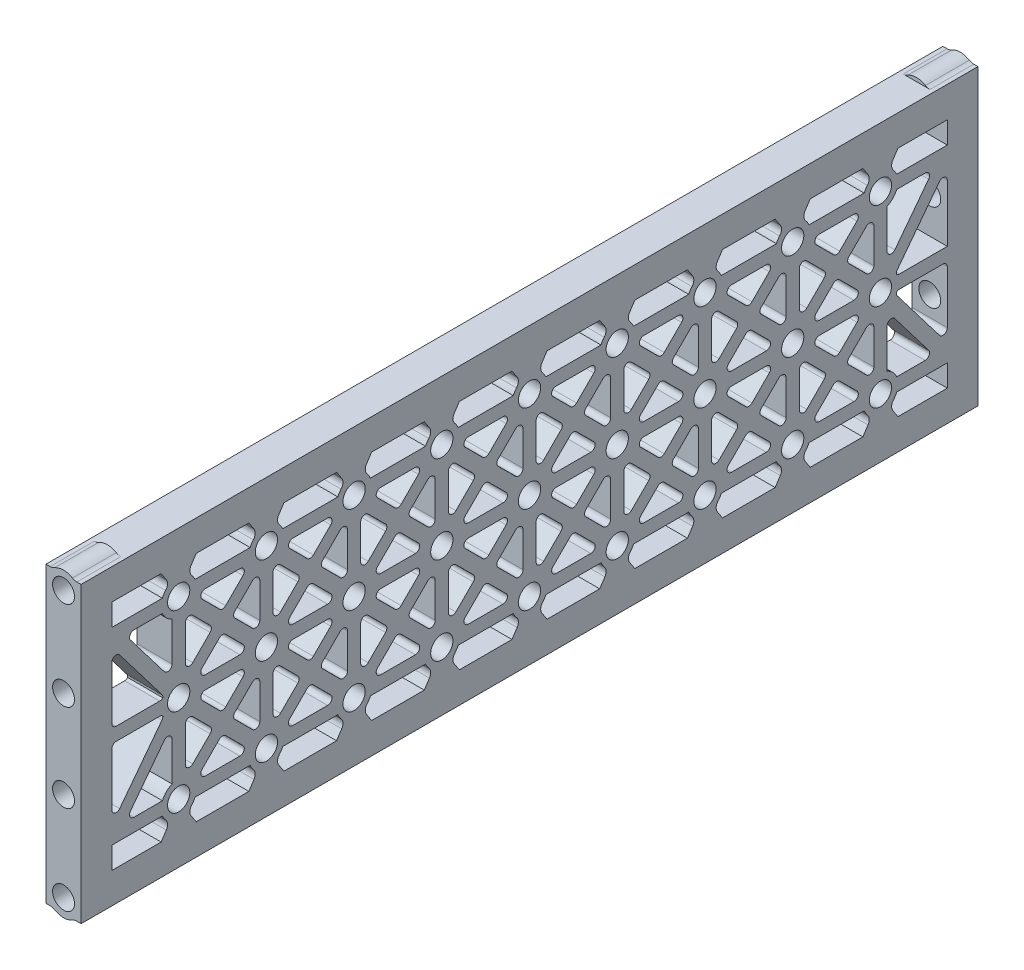
SolidWorks part; units mm, degrees
ref_plane "Front Plane" through (0, 0, 0) normal (0, 0, 1) x (1, 0, 0)
ref_plane "Top Plane" through (0, 0, 0) normal (0, 1, 0) x (1, 0, 0)
ref_plane "Right Plane" through (0, 0, 0) normal (1, 0, 0) x (0, 0, -1)
sketch "Sketch1" plane through (-219.25, 0, 0) normal (-1, 0, 0) x (0, 0, 1)
  line L1 (102.25, 62) -> (-102.25, 62)
  line L2 (102.25, 62) -> (102.25, -5)
  line L3 (102.25, -5) -> (-102.25, -5)
  line L4 (-102.25, 62) -> (-102.25, -5)
  line L5 (102.25, 1.35) -> (102.25, -6.9319) construction
  line L6 (110.25, 62) -> (102.25, 62) construction
  line L7 (-102.25, -5) -> (-102.25, 0) construction
  line L8 (-102.25, -5) -> (-110.25, -5) construction
extrude "Boss-Extrude1" add sketch "Sketch1" against normal blind 8
hole_wizard "Ø5.0mm Dowel Hole1" positions "Sketch4" profile "Sketch3" hole size "Ø5.0" standard "ANSI Metric"
sketch "Sketch4" plane through (0, 0, 102.25) normal (0, 0, 1) x (1, 0, 0)
  point P0 (-215.25, 58.825)
  point P3 (-215.25, 38.5)
  point P6 (-215.25, 18.5)
  point P9 (-215.25, -1.825)
sketch "Sketch3" plane through (-215.25, 58.825, 102.25) normal (1, 0, 0) x (0, -1, 0)
  line L0 (0, 0) -> (0, 11.5022)
  line L1 (0, 11.5022) -> (2.5, 10)
  line L2 (2.5, 10) -> (2.5, 0)
  line L5 (2.5, 0) -> (0, 0)
  line L10 (0, 11.5022) -> (-2.5, 10) construction
  line L11 (0, -6.35) -> (0, 107.95) construction
  dimension "Hole Dia." = 5
  dimension "Hole Depth" = 10
  dimension "Drill Angle" = 118
sketch "Sketch5" plane through (0, 0, 102.25) normal (0, 0, 1) x (1, 0, 0)
  circle A0 centre (-215.25, 58.825) radius 4
  circle A1 centre (-215.25, -1.825) radius 4
  line M6 (-219.25, -5) -> (-211.25, -5)
  line M8 (-211.25, 62) -> (-219.25, 62)
extrude "Boss-Extrude2" add sketch "Sketch5" against normal blind 10 contours A1 M6 | A0 M8 region at (-215.25, 62.3331, 102.25) region at (-215.25, -5.3331, 102.25)
fillet "Fillet1" radius 2 4 edges at (-212.817, -5, 97.25) (-217.683, -5, 97.25) (-212.817, 62, 97.25) (-217.683, 62, 97.25)
mirror "Mirror1" about plane through (0, 0, 0) normal (0, 0, 1) of "Fillet1", "Boss-Extrude2", "Ø5.0mm Dowel Hole1"
sketch "Sketch6" plane through (-219.25, 0, 0) normal (-1, 0, 0) x (0, 0, 1)
  line L0 (0, 8.5) -> (0, 28.5) construction
  line L1 (0, 48.5) -> (0, 55) construction
  line L2 (0, 8.5) -> (20, 8.5) construction
  line L3 (0, -4.4) -> (0, 4.4) construction
  line L10 (0, 8.5) -> (0, 2) construction
  line L14 (95.25, 2) -> (95.25, 55)
  line L15 (-95.25, 2) -> (95.25, 2)
  line L16 (-95.25, 55) -> (-95.25, 2)
  line L17 (95.25, 55) -> (-95.25, 55)
  line L18 (95.25, 2) -> (95.25, 55)
  line L19 (-95.25, 2) -> (95.25, 2)
  line L20 (-95.25, 55) -> (-95.25, 2)
  line L21 (95.25, 55) -> (-95.25, 55)
  circle A0 centre (0, 8.5) radius 2.54
  circle A1 centre (0, 28.5) radius 2.54
  circle A2 centre (0, 48.5) radius 2.54
  circle A3 centre (0, 48.5) radius 4
  circle A4 centre (0, 28.5) radius 4
  circle A5 centre (0, 8.5) radius 4
  circle A6 centre (20, 8.5) radius 4
  circle A7 centre (20, 8.5) radius 2.54
  circle A8 centre (20, 28.5) radius 4
  circle A9 centre (20, 28.5) radius 2.54
  circle A10 centre (20, 48.5) radius 2.54
  circle A11 centre (20, 48.5) radius 4
  circle A12 centre (40, 8.5) radius 4
  circle A13 centre (40, 8.5) radius 2.54
  circle A14 centre (40, 28.5) radius 4
  circle A15 centre (40, 28.5) radius 2.54
  circle A16 centre (40, 48.5) radius 2.54
  circle A17 centre (40, 48.5) radius 4
  circle A18 centre (60, 8.5) radius 4
  circle A19 centre (60, 8.5) radius 2.54
  circle A20 centre (60, 28.5) radius 4
  circle A21 centre (60, 28.5) radius 2.54
  circle A22 centre (60, 48.5) radius 2.54
  circle A23 centre (60, 48.5) radius 4
  circle A24 centre (80, 8.5) radius 4
  circle A25 centre (80, 8.5) radius 2.54
  circle A26 centre (80, 28.5) radius 4
  circle A27 centre (80, 28.5) radius 2.54
  circle A28 centre (80, 48.5) radius 2.54
  circle A29 centre (80, 48.5) radius 4
  circle A30 centre (-20, 8.5) radius 4
  circle A31 centre (-20, 8.5) radius 2.54
  circle A32 centre (-40, 8.5) radius 4
  circle A33 centre (-40, 8.5) radius 2.54
  circle A34 centre (-60, 8.5) radius 4
  circle A35 centre (-60, 8.5) radius 2.54
  circle A36 centre (-80, 8.5) radius 4
  circle A37 centre (-80, 8.5) radius 2.54
  circle A38 centre (-80, 48.5) radius 2.54
  circle A39 centre (-80, 48.5) radius 4
  circle A40 centre (-80, 28.5) radius 4
  circle A41 centre (-80, 28.5) radius 2.54
  circle A42 centre (-60, 28.5) radius 2.54
  circle A43 centre (-60, 28.5) radius 4
  circle A44 centre (-40, 28.5) radius 4
  circle A45 centre (-40, 28.5) radius 2.54
  circle A46 centre (-20, 28.5) radius 4
  circle A47 centre (-20, 28.5) radius 2.54
  circle A48 centre (-20, 48.5) radius 2.54
  circle A49 centre (-20, 48.5) radius 4
  circle A50 centre (-40, 48.5) radius 2.54
  circle A51 centre (-40, 48.5) radius 4
  circle A52 centre (-60, 48.5) radius 4
  circle A53 centre (-60, 48.5) radius 2.54
  dimension "D2" = 5.08
  dimension "D5" = 8
  dimension "D4" = 20
  dimension "D7" = 20
  dimension "D1" = 7
  dimension "D3" = 3
  dimension "D6" = 5
extrude "Cut-Extrude1" cut sketch "Sketch6" against normal through all contours L18 L21 L20 L19 A51 A49 A46 A43 A40 A34 A30 A29 A26 A24 A23 A20 A18 A17 A14 A12 A11 A8 A6 A5 A4 A3 A32 | A38 | A53 | A50 | A48 | A47 | A45 | A42 | A41 | A0 | A1 | A2 | A9 | A7 | A31 | A33 | A35 | A37 | A16 | A22 | A28 | A10 | A15 | A21 | A27 | A25 | A19 | A13 region at (-219.25, 3.9774, 0) region at (-219.25, 8.5, 0) region at (-219.25, 28.5, 0) region at (-219.25, 48.5, 0) region at (-219.25, 8.5, 20) region at (-219.25, 28.5, 20) region at (-219.25, 48.5, 20) region at (-219.25, 8.5, 40) region at (-219.25, 28.5, 40) region at (-219.25, 48.5, 40) region at (-219.25, 8.5, 60) region at (-219.25, 28.5, 60) region at (-219.25, 48.5, 60) region at (-219.25, 8.5, 80) region at (-219.25, 28.5, 80) region at (-219.25, 48.5, 80) region at (-219.25, 8.5, -20) region at (-219.25, 8.5, -40) region at (-219.25, 8.5, -60) region at (-219.25, 8.5, -80) region at (-219.25, 48.5, -80) region at (-219.25, 28.5, -80) region at (-219.25, 28.5, -60) region at (-219.25, 28.5, -40) region at (-219.25, 28.5, -20) region at (-219.25, 48.5, -20) region at (-219.25, 48.5, -40) region at (-219.25, 48.5, -60)
sketch "Sketch7" plane through (-219.25, 0, 0) normal (-1, 0, 0) x (0, 0, 1)
  line L0 (80, 45.96) -> (80, 31.04) construction
  line L1 (60, 45.96) -> (60, 31.04) construction
  line L2 (62.54, 48.5) -> (77.46, 48.5) construction
  line L3 (62.54, 28.5) -> (77.46, 28.5) construction
  line L4 (70, 38.5) -> (78.2039, 46.7039) construction
  line L5 (61.7961, 46.7039) -> (70, 38.5) construction
  line L6 (61.7961, 30.2961) -> (70, 38.5) construction
  line L7 (70, 38.5) -> (78.2039, 30.2961) construction
  line L8 (65.3284, 45.2929) -> (69.2929, 41.3284)
  line L9 (70.7071, 41.3284) -> (74.6716, 45.2929)
  line L10 (66.0355, 47) -> (73.9645, 47)
  line L11 (62.8567, 47.7646) -> (70, 40.6213) construction
  line L12 (62.54, 47) -> (77.46, 47) construction
  line L13 (70, 40.6213) -> (77.1433, 47.7646) construction
  line L14 (76.7929, 43.1716) -> (72.8284, 39.2071)
  line L15 (72.8284, 37.7929) -> (76.7929, 33.8284)
  line L16 (78.5, 42.4645) -> (78.5, 34.5355)
  line L17 (74.6716, 31.7071) -> (70.7071, 35.6716)
  line L18 (69.2929, 35.6716) -> (65.3284, 31.7071)
  line L19 (73.9645, 30) -> (66.0355, 30)
  line L20 (63.2071, 33.8284) -> (67.1716, 37.7929)
  line L21 (67.1716, 39.2071) -> (63.2071, 43.1716)
  line L22 (61.5, 34.5355) -> (61.5, 42.4645)
  line L23 (63.7081, 50) -> (76.2919, 50)
  line L24 (81.5, 44.7919) -> (81.5, 32.2081)
  line L25 (58.5, 44.7919) -> (58.5, 32.2081)
  line L26 (62.54, 27) -> (76.2919, 27)
  line L27 (62.54, 50) -> (77.46, 50) construction
  line L28 (58.5, 45.96) -> (58.5, 31.04) construction
  line L29 (81.5, 45.96) -> (81.5, 31.04) construction
  line L30 (62.54, 27) -> (77.46, 27) construction
  circle A0 centre (80, 48.5) radius 2.54 construction
  circle A1 centre (80, 28.5) radius 2.54 construction
  circle A2 centre (60, 48.5) radius 2.54 construction
  circle A3 centre (60, 28.5) radius 2.54 construction
  arc A4 (80, 31.04) -> (77.46, 28.5) centre (80, 28.5) ccw construction
  arc A5 (77.46, 48.5) -> (80, 45.96) centre (80, 48.5) ccw construction
  arc A6 (60, 45.96) -> (62.54, 48.5) centre (60, 48.5) ccw construction
  arc A7 (62.54, 28.5) -> (60, 31.04) centre (60, 28.5) ccw construction
  arc A8 (73.9645, 47) -> (74.6716, 45.2929) centre (73.9645, 46) cw
  arc A9 (70.7071, 41.3284) -> (69.2929, 41.3284) centre (70, 42.0355) cw
  arc A10 (65.3284, 45.2929) -> (66.0355, 47) centre (66.0355, 46) cw
  arc A11 (76.7929, 43.1716) -> (78.5, 42.4645) centre (77.5, 42.4645) cw
  arc A12 (72.8284, 37.7929) -> (72.8284, 39.2071) centre (73.5355, 38.5) cw
  arc A13 (78.5, 34.5355) -> (76.7929, 33.8284) centre (77.5, 34.5355) cw
  arc A14 (74.6716, 31.7071) -> (73.9645, 30) centre (73.9645, 31) cw
  arc A15 (69.2929, 35.6716) -> (70.7071, 35.6716) centre (70, 34.9645) cw
  arc A16 (66.0355, 30) -> (65.3284, 31.7071) centre (66.0355, 31) cw
  arc A17 (63.2071, 33.8284) -> (61.5, 34.5355) centre (62.5, 34.5355) cw
  arc A18 (67.1716, 39.2071) -> (67.1716, 37.7929) centre (66.4645, 38.5) cw
  arc A19 (61.5, 42.4645) -> (63.2071, 43.1716) centre (62.5, 42.4645) cw
  circle A20 centre (60, 28.5) radius 4 construction
  circle A21 centre (80, 28.5) radius 4 construction
  circle A22 centre (80, 48.5) radius 4 construction
  circle A23 centre (60, 48.5) radius 4 construction
  circle A24 centre (60, 28.5) radius 4
  circle A25 centre (80, 28.5) radius 4
  circle A26 centre (80, 48.5) radius 4
  circle A27 centre (60, 48.5) radius 4
  point P40 (70, 38.5)
  point P69 (70, 38.5)
  circle M37 centre (80, 48.5) radius 4
  dimension "D3" = 1
  dimension "D1" = 1.5
  dimension "D2" = 1.5
  dimension "D5" = 1.5
  dimension "D6" = 1.5
  dimension "D4" = 4
extrude "Boss-Extrude3" add sketch "Sketch7" against normal up to surface (8 mm away) contours A27 L25 A24 L26 A25 L24 L23 L8 A10 L10 A8 L9 A9 L16 A13 L15 A12 L14 A11 L19 A16 L18 A15 L17 A14 L22 A19 L21 A18 L20 A17 M37 region at (-219.25, 38.5, 70) up to face at (-211.25, 48.5, 64)
pattern_linear "LPattern1" count 8 spacing 20 along (0, 0, -1) count 2 spacing 20 along (0, -1, 0) of "Boss-Extrude3"
sketch "Sketch8" plane through (-219.25, 0, 0) normal (-1, 0, 0) x (0, 0, 1)
  line L0 (80, 48.5) -> (95.25, 48.5) construction
  line L1 (95.25, 2) -> (95.25, 55) construction
  line L2 (80, 28.5) -> (95.25, 28.5) construction
  line L3 (80, 8.5) -> (95.25, 8.5) construction
  line L4 (83.7081, 47) -> (92.2199, 47)
  line L6 (80, 28.5) -> (95.25, 48.5) construction
  line L7 (80, 28.5) -> (95.25, 8.5) construction
  line L8 (81.0556, 32.3582) -> (92.2199, 47)
  line L9 (80, 10) -> (92.2199, 10) construction
  line L10 (81.0556, 24.6418) -> (92.2199, 10)
  line L11 (83.7081, 10) -> (92.2199, 10)
  line L12 (83.7081, 50) -> (95.25, 50)
  line L13 (83.7081, 27) -> (95.25, 27)
  line L14 (81.1928, 29.4095) -> (98.2801, 7) construction
  line L15 (83.4412, 26.4608) -> (95.25, 10.9738)
  line L16 (83.7081, 7) -> (95.25, 7)
  line L17 (95.25, 50) -> (95.25, 7)
  line L18 (80, 50) -> (98.2801, 50) construction
  line L19 (80, 47) -> (92.2199, 47) construction
  line L20 (78.8072, 29.4095) -> (92.2199, 47) construction
  line L21 (83.7081, 30) -> (95.25, 30)
  line L23 (83.4412, 30.5392) -> (95.25, 46.0262)
  line L24 (81.1928, 27.5905) -> (98.2801, 50) construction
  line L25 (78.8072, 27.5905) -> (92.2199, 10) construction
  line L26 (80, 7) -> (98.2801, 7) construction
  circle A5 centre (80, 28.5) radius 4
  circle A6 centre (80, 48.5) radius 4
  circle A7 centre (80, 8.5) radius 4
  line M14 (95.25, 55) -> (95.25, 2)
  dimension "D1" = 1.5
  dimension "D2" = 1.5
extrude "Boss-Extrude4" add sketch "Sketch8" against normal up to surface (8 mm away) contours A6 L4 L8 A5 L23 L12 M14 | A5 L13 L17 L21 | A7 L16 L15 A5 L10 L11 M14 region at (-219.25, 47.6899, 84.1628) region at (-219.25, 25.1276, 82.5714) region at (-219.25, 28.5, 89.5768) up to face at (-211.25, 28.5, 0)
mirror "Mirror2" about plane through (0, 0, 0) normal (0, 0, 1) of "Boss-Extrude4"
fillet "Fillet2" radius 1 23 edges at (-215.25, 10, 92.2199) (-215.25, 10.9738, 95.25) (-215.25, 24.0589, 81.5) (-215.25, 27, 95.25) (-215.25, 30, 95.25) (-215.25, 46.0262, 95.25) (-215.25, 26.4608, 83.4412) (-215.25, 27, 83.7081) (-215.25, 30.5392, 83.4412) (-215.25, 30, 83.7081) (-215.25, 32.9411, 81.5) (-215.25, 47, 92.2199) (-215.25, 47, -92.2199) (-215.25, 32.9411, -81.5) (-215.25, 30, -83.7081) (-215.25, 30.5392, -83.4412) (-215.25, 26.4608, -83.4412) (-215.25, 27, -83.7081) (-215.25, 10.9738, -95.25) (-215.25, 10, -92.2199) (-215.25, 24.0589, -81.5) (-215.25, 27, -95.25) (-215.25, 46.0262, -95.25)
sketch "Sketch9" plane through (-219.25, 0, 0) normal (-1, 0, 0) x (0, 0, 1)
  line L0 (78, 51.9641) -> (82, 51.9641) construction
  line L1 (78, 51.9641) -> (76, 55)
  line L2 (95.25, 55) -> (-95.25, 55) construction
  line L3 (76, 55) -> (84, 55)
  line L4 (84, 55) -> (82, 51.9641)
  line L5 (82, 51.9641) -> (78, 51.9641)
  arc A0 (83.7081, 50) -> (76.2919, 50) centre (80, 48.5) ccw construction
  arc A1 (82.8252, 53.2167) -> (82.9775, 51.171) centre (84.2279, 52.2926) ccw
  arc A2 (77.1748, 53.2167) -> (77.0225, 51.171) centre (75.7721, 52.2926) cw
  arc A3 (83.7081, 50) -> (76.2919, 50) centre (80, 48.5) ccw
  dimension "D1" = 4
  dimension "D2" = 8
  dimension "D3" = 1.5
extrude "Boss-Extrude5" add sketch "Sketch9" against normal up to surface (8 mm away) contours A3 L4 L3 L1 | A3 L1 A2 | A3 A1 L4 region at (-219.25, 52.0929, 77.58) region at (-219.25, 53.7779, 80) region at (-219.25, 52.0929, 82.42) up to face at (-211.25, 22.7928, -90.0425)
pattern_linear "LPattern2" count 9 spacing 20 along (0, 0, -1) of "Boss-Extrude5"
ref_plane "Plane1" through (0, 28.5, 0) normal (0, 1, 0) x (1, 0, 0)
mirror "Mirror3" about plane through (0, 28.5, 0) normal (0, 1, 0) of "LPattern2", "Boss-Extrude5"
